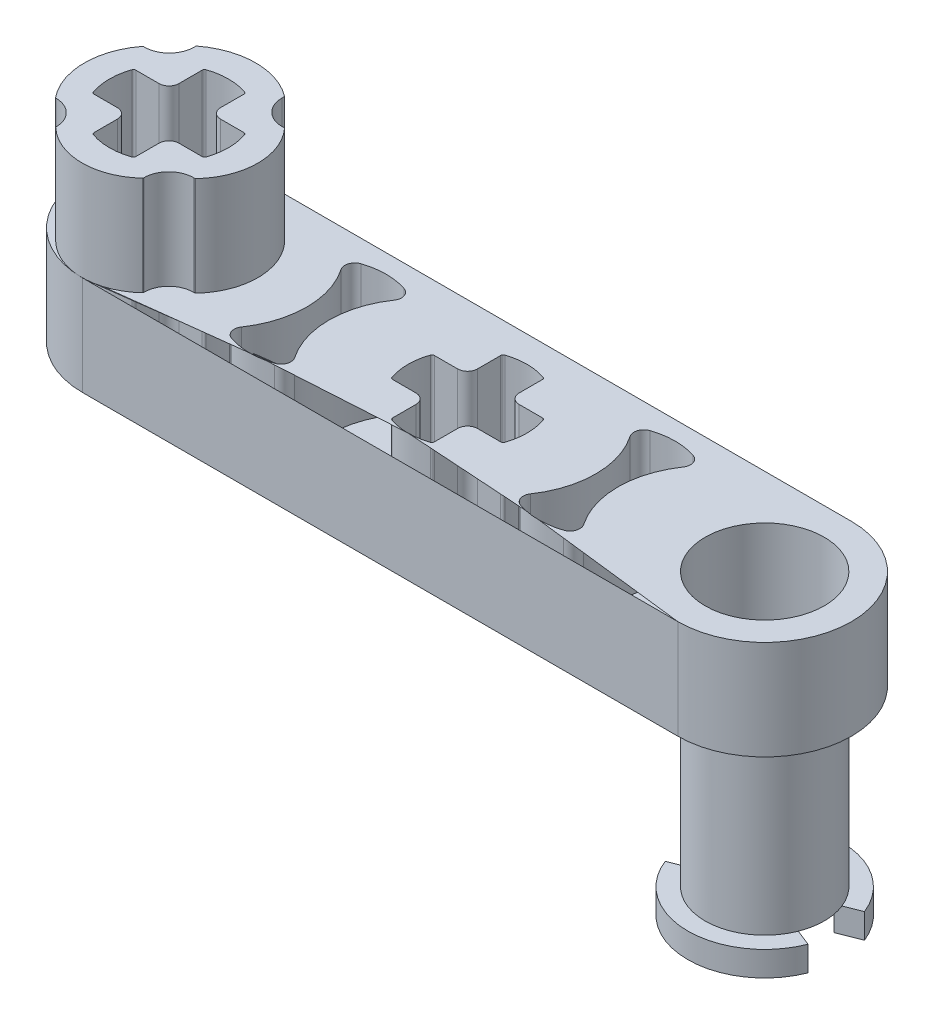
SolidWorks part; units mm, degrees
ref_plane "Front Plane" through (0, 0, 0) normal (0, 0, 1) x (1, 0, 0)
ref_plane "Top Plane" through (0, 0, 0) normal (0, 1, 0) x (1, 0, 0)
ref_plane "Right Plane" through (0, 0, 0) normal (1, 0, 0) x (0, 0, -1)
sketch "Sketch2" plane through (0, 0, 0) normal (0, 1, 0) x (1, 0, 0)
  line L3 (-5.28, -1.2531) -> (-5.28, -2.1908)
  line L4 (-5.28, 2.1646) -> (-5.28, 1.2269)
  line L5 (-3.6, 2.1646) -> (-3.6, 1.2269)
  line L6 (-6.6177, 0.8269) -> (-5.68, 0.8269)
  line L7 (-6.6177, -0.8531) -> (-5.68, -0.8531)
  line L8 (-3.2, 0.8269) -> (-2.2623, 0.8269)
  line L9 (-3.6, -1.2531) -> (-3.6, -2.1908)
  line L10 (-3.2, -0.8531) -> (-2.2623, -0.8531)
  line L21 (-4.44, 3.5) -> (19.56, 3.5)
  line L29 (6.6979, -1.1956) -> (6.6979, -2.1333)
  line L30 (6.6979, 2.2221) -> (6.6979, 1.2844)
  line L31 (8.3779, 2.2221) -> (8.3779, 1.2844)
  line L32 (5.3602, 0.8844) -> (6.2979, 0.8844)
  line L33 (5.3602, -0.7956) -> (6.2979, -0.7956)
  line L34 (8.7779, 0.8844) -> (9.7156, 0.8844)
  line L35 (8.3779, -1.1956) -> (8.3779, -2.1333)
  line L36 (8.7779, -0.7956) -> (9.7156, -0.7956)
  line L37 (-4.44, -3.5) -> (19.56, -3.5)
  arc A2 (-3.6678, 2.2593) -> (-5.2121, 2.2593) centre (-4.44, -0.0131) ccw
  arc A3 (-6.7124, 0.759) -> (-6.7124, -0.7853) centre (-4.44, -0.0131) ccw
  arc A4 (-2.1676, -0.7853) -> (-2.1676, 0.759) centre (-4.44, -0.0131) ccw
  arc A5 (-5.2121, -2.2855) -> (-3.6678, -2.2855) centre (-4.44, -0.0131) ccw
  arc A6 (-6.6177, 0.8269) -> (-6.7124, 0.759) centre (-6.6177, 0.7269) ccw
  arc A7 (-6.7124, -0.7853) -> (-6.6177, -0.8531) centre (-6.6177, -0.7531) ccw
  arc A8 (-5.28, -2.1908) -> (-5.2121, -2.2855) centre (-5.18, -2.1908) ccw
  arc A9 (-3.6678, -2.2855) -> (-3.6, -2.1908) centre (-3.7, -2.1908) ccw
  arc A10 (-2.2623, -0.8531) -> (-2.1676, -0.7853) centre (-2.2623, -0.7531) ccw
  arc A11 (-2.2623, 0.8269) -> (-2.1676, 0.759) centre (-2.2623, 0.7269) cw
  arc A12 (-3.6678, 2.2593) -> (-3.6, 2.1646) centre (-3.7, 2.1646) cw
  arc A13 (-5.2121, 2.2593) -> (-5.28, 2.1646) centre (-5.18, 2.1646) ccw
  arc A14 (-5.28, -1.2531) -> (-5.68, -0.8531) centre (-5.68, -1.2531) ccw
  arc A15 (-3.6, -1.2531) -> (-3.2, -0.8531) centre (-3.2, -1.2531) cw
  arc A16 (-3.2, 0.8269) -> (-3.6, 1.2269) centre (-3.2, 1.2269) cw
  arc A17 (-5.68, 0.8269) -> (-5.28, 1.2269) centre (-5.68, 1.2269) ccw
  circle A34 centre (19.56, 0) radius 2.4
  arc A41 (-4.44, 3.5) -> (-4.44, -3.5) centre (-4.44, 0) ccw
  arc A50 (8.31, 2.3168) -> (6.7657, 2.3168) centre (7.5379, 0.0444) ccw
  arc A51 (5.2655, 0.8166) -> (5.2655, -0.7278) centre (7.5379, 0.0444) ccw
  arc A52 (9.8102, -0.7278) -> (9.8102, 0.8166) centre (7.5379, 0.0444) ccw
  arc A53 (6.7657, -2.228) -> (8.31, -2.228) centre (7.5379, 0.0444) ccw
  arc A54 (5.3602, 0.8844) -> (5.2655, 0.8166) centre (5.3602, 0.7844) ccw
  arc A55 (5.2655, -0.7278) -> (5.3602, -0.7956) centre (5.3602, -0.6956) ccw
  arc A56 (6.6979, -2.1333) -> (6.7657, -2.228) centre (6.7979, -2.1333) ccw
  arc A57 (8.31, -2.228) -> (8.3779, -2.1333) centre (8.2779, -2.1333) ccw
  arc A58 (9.7156, -0.7956) -> (9.8102, -0.7278) centre (9.7156, -0.6956) ccw
  arc A59 (9.7156, 0.8844) -> (9.8102, 0.8166) centre (9.7156, 0.7844) cw
  arc A60 (8.31, 2.3168) -> (8.3779, 2.2221) centre (8.2779, 2.2221) cw
  arc A61 (6.7657, 2.3168) -> (6.6979, 2.2221) centre (6.7979, 2.2221) ccw
  arc A62 (6.6979, -1.1956) -> (6.2979, -0.7956) centre (6.2979, -1.1956) ccw
  arc A63 (8.3779, -1.1956) -> (8.7779, -0.7956) centre (8.7779, -1.1956) cw
  arc A64 (8.7779, 0.8844) -> (8.3779, 1.2844) centre (8.7779, 1.2844) cw
  arc A65 (6.2979, 0.8844) -> (6.6979, 1.2844) centre (6.2979, 1.2844) ccw
  arc A66 (19.56, 3.5) -> (19.56, -3.5) centre (19.56, 0) cw
  arc A67 (0.683, -2.6101) -> (2.4149, -2.6101) centre (1.5489, 0) ccw
  arc A68 (2.6191, -2.0046) -> (2.4149, -2.6101) centre (2.2889, -2.2304) cw
  arc A69 (2.6191, -2.0046) -> (2.6191, 2.0046) centre (5.5489, 0) cw
  arc A70 (2.6191, 2.0046) -> (2.4149, 2.6101) centre (2.2889, 2.2304) ccw
  arc A71 (2.4149, 2.6101) -> (0.683, 2.6101) centre (1.5489, 0) ccw
  arc A72 (0.4788, 2.0046) -> (0.683, 2.6101) centre (0.8089, 2.2304) cw
  arc A73 (0.4788, -2.0046) -> (0.4788, 2.0046) centre (-2.4511, 0) ccw
  arc A74 (0.4788, -2.0046) -> (0.683, -2.6101) centre (0.8089, -2.2304) ccw
  arc A75 (12.333, -2.6101) -> (14.0649, -2.6101) centre (13.1989, 0) ccw
  arc A76 (14.2691, -2.0046) -> (14.0649, -2.6101) centre (13.9389, -2.2304) cw
  arc A77 (14.2691, -2.0046) -> (14.2691, 2.0046) centre (17.1989, 0) cw
  arc A78 (14.2691, 2.0046) -> (14.0649, 2.6101) centre (13.9389, 2.2304) ccw
  arc A79 (14.0649, 2.6101) -> (12.333, 2.6101) centre (13.1989, 0) ccw
  arc A80 (12.1288, 2.0046) -> (12.333, 2.6101) centre (12.4589, 2.2304) cw
  arc A81 (12.1288, -2.0046) -> (12.1288, 2.0046) centre (9.1989, 0) ccw
  arc A82 (12.1288, -2.0046) -> (12.333, -2.6101) centre (12.4589, -2.2304) ccw
  point P88 (7.56, 0)
  dimension "D4" = 4.8
extrude "Boss-Extrude1" add sketch "Sketch2" along normal mid plane 4
sketch "Sketch3" plane through (0, 2, 0) normal (0, 1, 0) x (1, 0, 0)
  line L9 (-2.6998, 2.8061) -> (-2.6998, 2.9087)
  line L10 (-6.2443, -2.7734) -> (-6.2443, -2.7616)
  line L11 (-2.6998, -2.7965) -> (-2.6998, -2.7616)
  line L12 (-1.6998, -1.7616) -> (-1.6326, -1.7616)
  line L13 (-7.3024, 1.8061) -> (-7.2443, 1.8061)
  line L14 (-7.267, -1.7616) -> (-7.2443, -1.7616)
  line L15 (-1.6998, 1.8061) -> (-1.5972, 1.8061)
  line L16 (-6.2443, 2.8061) -> (-6.2443, 2.8857)
  arc A8 (-2.6998, 2.8061) -> (-1.6998, 1.8061) centre (-1.6998, 2.8061) ccw
  arc A9 (-1.6998, -1.7616) -> (-2.6998, -2.7616) centre (-1.6998, -2.7616) ccw
  arc A10 (-6.2443, -2.7616) -> (-7.2443, -1.7616) centre (-7.2443, -2.7616) ccw
  arc A11 (-6.2443, 2.8061) -> (-7.2443, 1.8061) centre (-7.2443, 2.8061) cw
  arc A12 (-7.3024, 1.8061) -> (-7.267, -1.7616) centre (-5.0421, 0.0445) ccw
  arc A13 (-6.2443, 2.8857) -> (-2.6998, 2.9087) centre (-4.4571, 0.5912) cw
  arc A14 (-1.6326, -1.7616) -> (-1.5972, 1.8061) centre (-3.52, 0.0412) ccw
  arc A15 (-6.2443, -2.7734) -> (-2.6998, -2.7965) centre (-4.46, -0.936) ccw
extrude "Boss-Extrude2" add sketch "Sketch3" along normal blind 4
extrude "Cut-Extrude1" cut sketch "Sketch2<2>" along normal blind 8 flip side to cut
sketch "Sketch2<2>" plane through (0, 0, 0) normal (0, 1, 0) x (1, 0, 0) same geometry as "Sketch2"
sketch "Sketch5" plane through (0, -2, 0) normal (0, -1, 0) x (1, 0, 0)
  circle A0 centre (19.56, 0) radius 2.4
  circle A1 centre (19.56, 0) radius 2.15
  dimension "D1" = 4.3
extrude "Boss-Extrude3" add sketch "Sketch5" along normal blind 7 separate body
sketch "Sketch6" plane through (0, -9, 0) normal (0, -1, 0) x (1, 0, 0)
  line L0 (16.6692, 1.1194) -> (17.5551, 0.7763)
  line L4 (17.5551, -0.7763) -> (16.6692, -1.1194)
  line L8 (21.56, 0.789) -> (22.4437, 1.1376)
  line L9 (21.56, -0.789) -> (22.4437, -1.1376)
  arc A2 (17.5551, 0.7763) -> (21.56, 0.789) centre (19.56, 0) cw
  arc A3 (16.6692, 1.1194) -> (22.4437, 1.1376) centre (19.56, 0) cw
  arc A4 (17.5551, -0.7763) -> (21.56, -0.789) centre (19.56, 0) ccw
  arc A5 (16.6692, -1.1194) -> (22.4437, -1.1376) centre (19.56, 0) ccw
extrude "Boss-Extrude4" add sketch "Sketch6" along normal blind 1
